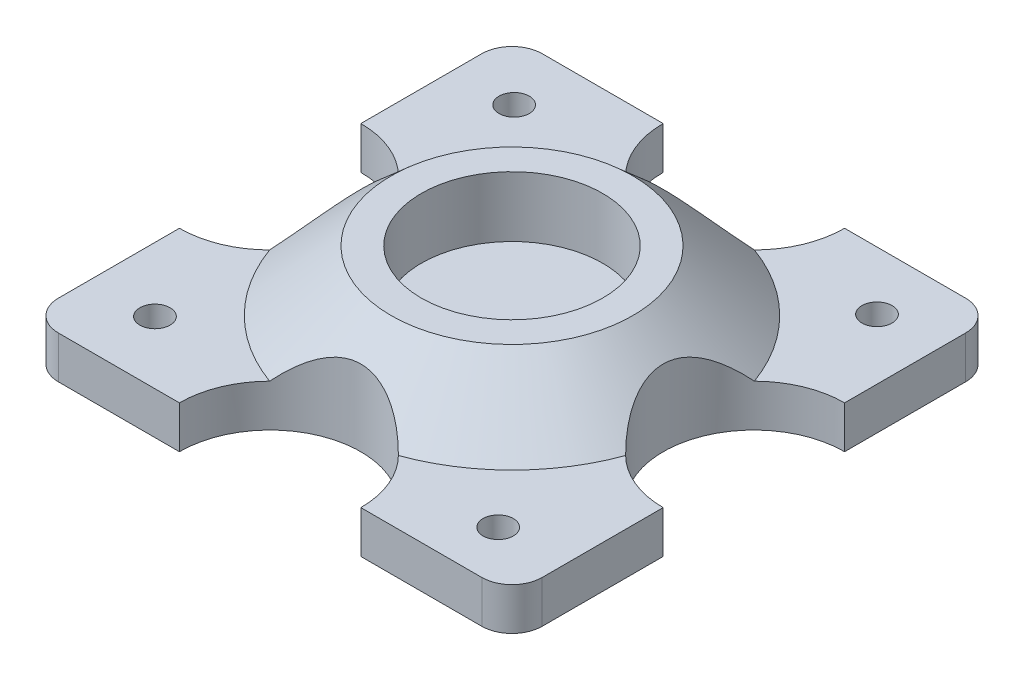
SolidWorks part; units mm, degrees
ref_plane "Front Plane" through (0, 0, 0) normal (0, 0, 1) x (1, 0, 0)
ref_plane "Top Plane" through (0, 0, 0) normal (0, 1, 0) x (1, 0, 0)
ref_plane "Right Plane" through (0, 0, 0) normal (1, 0, 0) x (0, 0, -1)
sketch "Sketch1" plane through (0, 0, 0) normal (0, 1, 0) x (1, 0, 0)
  line L1 (-44.45, 50.8) -> (44.45, 50.8)
  line L2 (-50.8, 44.45) -> (-50.8, -44.45)
  line L3 (-44.45, -50.8) -> (44.45, -50.8)
  line L4 (50.8, 44.45) -> (50.8, -44.45)
  line L5 (-50.8, 50.8) -> (50.8, -50.8) construction
  line L6 (-50.8, -50.8) -> (50.8, 50.8) construction
  arc A0 (44.45, -50.8) -> (50.8, -44.45) centre (44.45, -44.45) ccw
  arc A1 (-50.8, -44.45) -> (-44.45, -50.8) centre (-44.45, -44.45) ccw
  arc A2 (-44.45, 50.8) -> (-50.8, 44.45) centre (-44.45, 44.45) ccw
  arc A3 (44.45, 50.8) -> (50.8, 44.45) centre (44.45, 44.45) cw
  point P0 (0, 0)
  dimension "D3" = 6.35
  dimension "D1" = 101.6
  dimension "D2" = 101.6
extrude "Boss-Extrude1" add sketch "Sketch1" along normal blind 8.89
sketch "Sketch2" plane through (0, 0, 0) normal (0, 0, 1) x (1, 0, 0)
  line L0 (0, 0) -> (0, 71.4379) construction
  line L1 (0, 0) -> (0, 21.59)
  line L2 (0, 21.59) -> (25.4, 21.59)
  line L3 (0, 0) -> (41.275, 7.5445)
  line L5 (25.4, 21.59) -> (41.275, 7.5445)
  dimension "D1" = 21.59
  dimension "D2" = 50.8
  dimension "D3" = 82.55
revolve "Revolve1" add sketch "Sketch2" angle 360 about L0
sketch "Sketch3" plane through (0, 0, 0) normal (0, 1, 0) x (1, 0, 0)
  line L0 (-50.8, 44.45) -> (-50.8, -44.45) construction
  line L1 (50.8, -44.45) -> (50.8, 44.45) construction
  line L2 (44.45, 50.8) -> (-44.45, 50.8) construction
  line L3 (-44.45, -50.8) -> (44.45, -50.8) construction
  line L4 (0, -50.8) -> (0, 50.8) construction
  line L5 (-50.8, 0) -> (50.8, 0) construction
  circle A0 centre (-50.8, 0) radius 19.05
  circle A1 centre (0, 0) radius 19.05
  circle A2 centre (50.8, 0) radius 19.05
  circle A3 centre (0, 50.8) radius 19.05
  circle A4 centre (0, -50.8) radius 19.05
  circle A5 centre (-38.1, 38.5508) radius 3.175
  circle A6 centre (38.1, 38.5508) radius 3.175
  circle A7 centre (37.0502, -39.9519) radius 3.175
  circle A8 centre (-37.3321, -37.6492) radius 3.175
  point P27 (0, 0)
  point P28 (0, 0)
  point P29 (-50.8, 0)
  dimension "D1" = 38.1
  dimension "D2" = 6.35
  dimension "D3" = 76.2
  dimension "D4" = 76.2
extrude "Cut-Extrude5" cut sketch "Sketch3" along normal blind 59.944 contours A4 | A2 | A3 | A0 | A6 | A5 | A8 | A7
extrude "Cut-Extrude7" cut sketch "Sketch3<9>" along normal blind 71.374
sketch "Sketch3<9>" plane through (0, 0, 0) normal (0, 1, 0) x (1, 0, 0) same geometry as "Sketch3"
extrude "Boss-Extrude2" add sketch "Sketch3<12>" along normal up to surface (8.89 mm away) contours A1 up to face at (-38.1, 8.89, -35.3758)
sketch "Sketch3<12>" plane through (0, 0, 0) normal (0, 1, 0) x (1, 0, 0) same geometry as "Sketch3"
